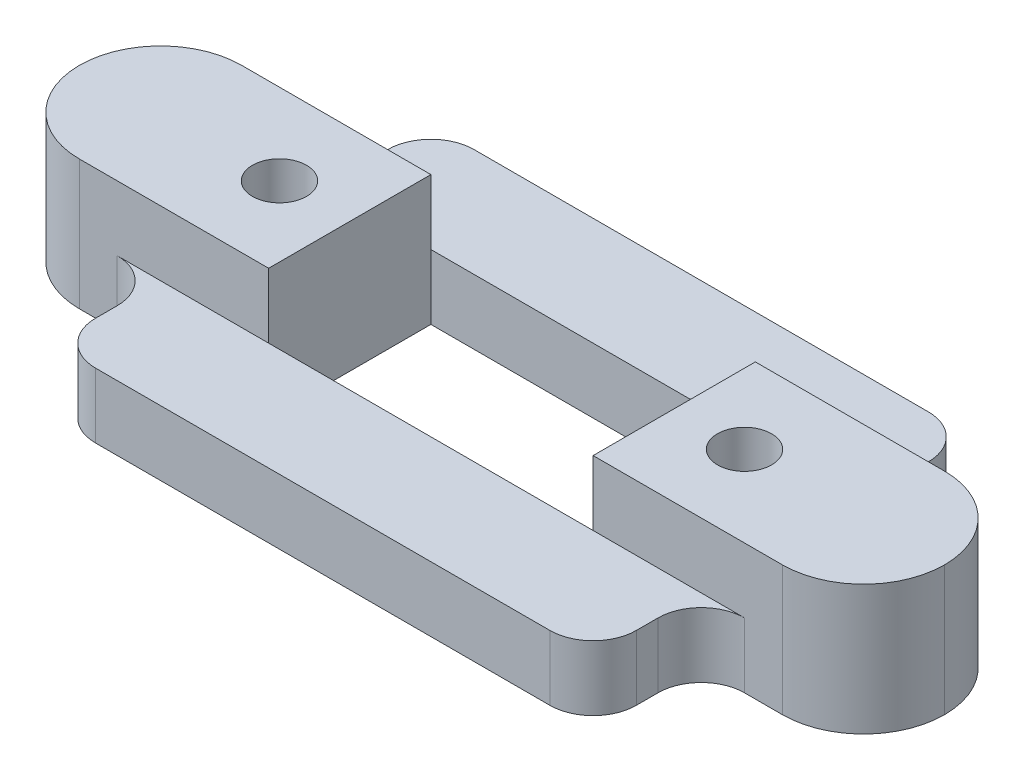
SolidWorks part; units mm, degrees
ref_plane "Front Plane" through (0, 0, 0) normal (0, 0, 1) x (1, 0, 0)
ref_plane "Top Plane" through (0, 0, 0) normal (0, 1, 0) x (1, 0, 0)
ref_plane "Right Plane" through (0, 0, 0) normal (1, 0, 0) x (0, 0, -1)
sketch "Sketch1" plane through (0, 0, 0) normal (0, 1, 0) x (1, 0, 0)
  line L1 (-20, 3.75) -> (-12.5, 3.75)
  line L2 (-20, 3.75) -> (-20, -3.75)
  line L3 (-20, -3.75) -> (-12.5, -3.75)
  line L4 (20, 3.75) -> (20, -3.75)
  line L5 (12.5, 3.75) -> (20, 3.75)
  line L6 (12.5, -3.75) -> (20, -3.75)
  line L7 (-7.5, 3.75) -> (7.5, 3.75)
  line L9 (-12.5, 3.75) -> (-12.5, 8.75)
  line L10 (-12.5, 8.75) -> (12.5, 8.75)
  line L11 (12.5, 8.75) -> (12.5, 3.75)
  line L16 (-12.5, -3.75) -> (-12.5, -8.75)
  line L17 (-12.5, -8.75) -> (12.5, -8.75)
  line L18 (12.5, -8.75) -> (12.5, -3.75)
  line L19 (-7.5, 3.75) -> (-7.5, -3.75)
  line L20 (-7.5, -3.75) -> (7.5, -3.75)
  line L21 (7.5, -3.75) -> (7.5, 3.75)
  point P0 (0, 0)
  dimension "D1" = 40
  dimension "D2" = 7.5
  dimension "D3" = 5
  dimension "D4" = 5
  dimension "D5" = 15
  dimension "D6" = 7.5
  dimension "D7" = 20
  dimension "D8" = 3.75
  dimension "D9" = 25
  dimension "D10" = 12.5
  dimension "D11" = 5
  dimension "D12" = 7.5
extrude "Boss-Extrude1" add sketch "Sketch1" along normal blind 6
sketch "Sketch2" plane through (0, 0, 0) normal (0, 1, 0) x (1, 0, 0)
  line L1 (0, -1.65) -> (0, 1.65) construction
  circle A0 centre (-10.75, 0) radius 1.25
  circle A6 centre (10.75, 0) radius 1.25
  dimension "D1" = 2.5
  dimension "D6" = 0
  dimension "D5" = 10.75
extrude "Cut-Extrude1" cut sketch "Sketch2" along normal blind 6
fillet "Fillet1" radius 3.75 4 edges at (-20, 3, 3.75) (-20, 3, -3.75) (20, 3, 3.75) (20, 3, -3.75)
sketch "Sketch3" plane through (0, 0, 0) normal (1, 0, 0) x (0, 0, -1)
  line L1 (8.75, 6) -> (3.75, 6)
  line L2 (8.75, 6) -> (8.75, 3)
  line L3 (8.75, 3) -> (3.75, 3)
  line L4 (3.75, 6) -> (3.75, 3)
  line L6 (-3.75, 6) -> (-8.75, 6)
  line L7 (-3.75, 6) -> (-3.75, 3)
  line L8 (-3.75, 3) -> (-8.75, 3)
  line L9 (-8.75, 6) -> (-8.75, 3)
  point P5 (0, 0)
  point P6 (0, 0)
  point P14 (0, 0)
  point P15 (0, 0)
  dimension "D1" = 3
  dimension "D2" = 5
  dimension "D3" = 5
  dimension "D4" = 3
  dimension "D5" = 3.75
  dimension "D6" = 3.75
  dimension "D7" = 3
  dimension "D8" = 3
extrude "Cut-Extrude2" cut sketch "Sketch3" against normal through all and the other way through all contours L2 L3 L4 L1 | L8 L9 L6 L7
fillet "Fillet2" radius 2 8 edges at (12.5, 1.5, -8.75) (12.5, 1.5, -3.75) (-12.5, 1.5, -8.75) (-12.5, 1.5, -3.75) (12.5, 1.5, 3.75) (12.5, 1.5, 8.75) (-12.5, 1.5, 8.75) (-12.5, 1.5, 3.75)
